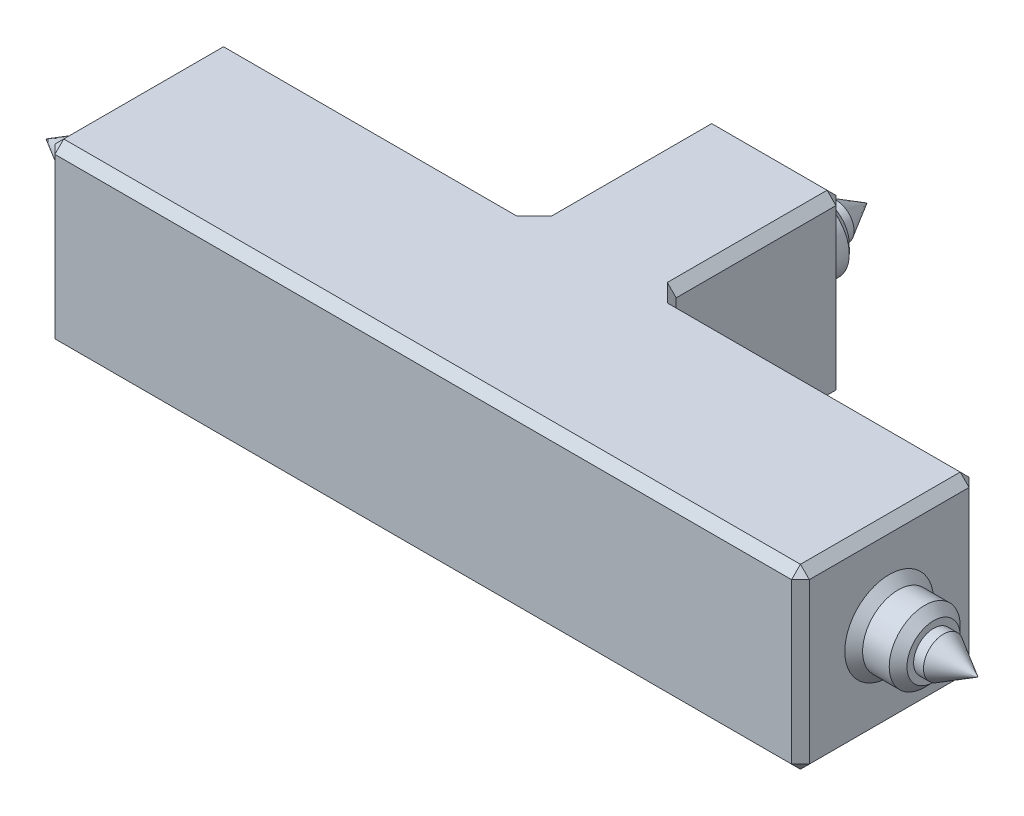
SolidWorks part; units mm, degrees
ref_plane "Front Plane" through (0, 0, 0) normal (0, 0, 1) x (1, 0, 0)
ref_plane "Top Plane" through (0, 0, 0) normal (0, 1, 0) x (1, 0, 0)
ref_plane "Right Plane" through (0, 0, 0) normal (1, 0, 0) x (0, 0, -1)
sketch "Sketch1" plane through (0, 0, 0) normal (0, 1, 0) x (1, 0, 0)
  line L0 (0, 0) -> (0, 34.8917) construction
  line L1 (-42.5, 0) -> (-42.5, -20)
  line L2 (-7.5, 20) -> (7.5, 20)
  line L3 (7.5, 20) -> (7.5, 0)
  line L4 (7.5, 0) -> (42.5, 0)
  line L5 (42.5, 0) -> (42.5, -20)
  line L6 (42.5, -20) -> (-42.5, -20)
  line L7 (-7.5, 0) -> (-42.5, 0)
  line L8 (-7.5, 20) -> (-7.5, 0)
  point P11 (0, -20)
  point P14 (0, 20)
  dimension "D2" = 7.5
  dimension "D3" = 20
  dimension "D4" = 35
  dimension "D5" = 20
extrude "Boss-Extrude1" add sketch "Sketch1" along normal blind 20
sketch "Sketch2" plane through (0, 0, -20) normal (0, 0, -1) x (-1, 0, 0)
  line L0 (-7.5, 20) -> (-7.5, 0) construction
  circle A0 centre (0, 10) radius 2
  circle A1 centre (0, 10) radius 4
  point P0 (-7.5, 10)
  point P1 (0, 10)
  dimension "D1" = 4
  dimension "D2" = 8
extrude "Boss-Extrude2" add sketch "Sketch2" along normal blind 5 contours A1 A0 region at (3.8869, 10, -20)
extrude "Boss-Extrude3" add sketch "Sketch2<4>" along normal blind 10 contours A0 region at (0, 10, -20)
sketch "Sketch2<4>" plane through (0, 0, -20) normal (0, 0, -1) x (-1, 0, 0) same geometry as "Sketch2"
sketch "Sketch3" plane through (-42.5, 0, 0) normal (-1, 0, 0) x (0, 0, 1)
  line L0 (0, 20) -> (0, 0) construction
  circle A0 centre (10, 10) radius 4
  circle A1 centre (10, 10) radius 1.75
  point P0 (0, 10)
  point P1 (10, 10)
  dimension "D1" = 8
  dimension "D2" = 3.5
extrude "Boss-Extrude4" add sketch "Sketch3" along normal blind 5
extrude "Boss-Extrude5" add sketch "Sketch3<2>" along normal blind 10 contours A1 region at (-42.5, 10, 10)
sketch "Sketch3<2>" plane through (-42.5, 0, 0) normal (-1, 0, 0) x (0, 0, 1) same geometry as "Sketch3"
sketch "Sketch4" plane through (42.5, 0, 0) normal (1, 0, 0) x (0, 0, -1)
  line L0 (-20, 0) -> (0, 0) construction
  circle A0 centre (-10, 10) radius 4
  circle A1 centre (-10, 10) radius 2.25
  point P0 (-10, 0)
  point P1 (-10, 10)
  dimension "D1" = 8
  dimension "D2" = 4.5
extrude "Boss-Extrude6" add sketch "Sketch4" along normal blind 5
extrude "Boss-Extrude7" add sketch "Sketch4<2>" along normal blind 10 contours A1 region at (42.5, 10, 10)
sketch "Sketch4<2>" plane through (42.5, 0, 0) normal (1, 0, 0) x (0, 0, -1) same geometry as "Sketch4"
chamfer "Chamfer1" distance 3.03 angle 30 1 edges at (-52.5, 10, 11.75) first distance on face at (-47.5, 10, 11.75)
chamfer "Chamfer2" distance 3.46 angle 30 1 edges at (-2, 10, -30) first distance on face at (-2, 10, -25)
chamfer "Chamfer3" distance 3.89 angle 30 1 edges at (52.5, 10, 7.75) first distance on face at (47.5, 10, 7.75)
chamfer "Chamfer4" distance 1 angle 45 30 edges at (42.5, 10, 14) (47.5, 10, 6) (4, 10, -20) (-4, 10, -25) (-42.5, 10, 14) (-47.5, 10, 14) (-42.5, 10, 20) (42.5, 10, 20) (7.5, 10, -20) (42.5, 10, 0) (7.5, 10, 0) (42.5, 0, 10) (25, 0, 0) (7.5, 0, -10) (0, 0, -20) (0, 0, 20) (-42.5, 0, 10) (-7.5, 10, -20) (-7.5, 0, -10) (-7.5, 10, 0) (-25, 0, 0) (-42.5, 10, 0) (-42.5, 20, 10) (-25, 20, 0) (-7.5, 20, -10) (0, 20, -20) (7.5, 20, -10) (25, 20, 0) (42.5, 20, 10) (0, 20, 20)
